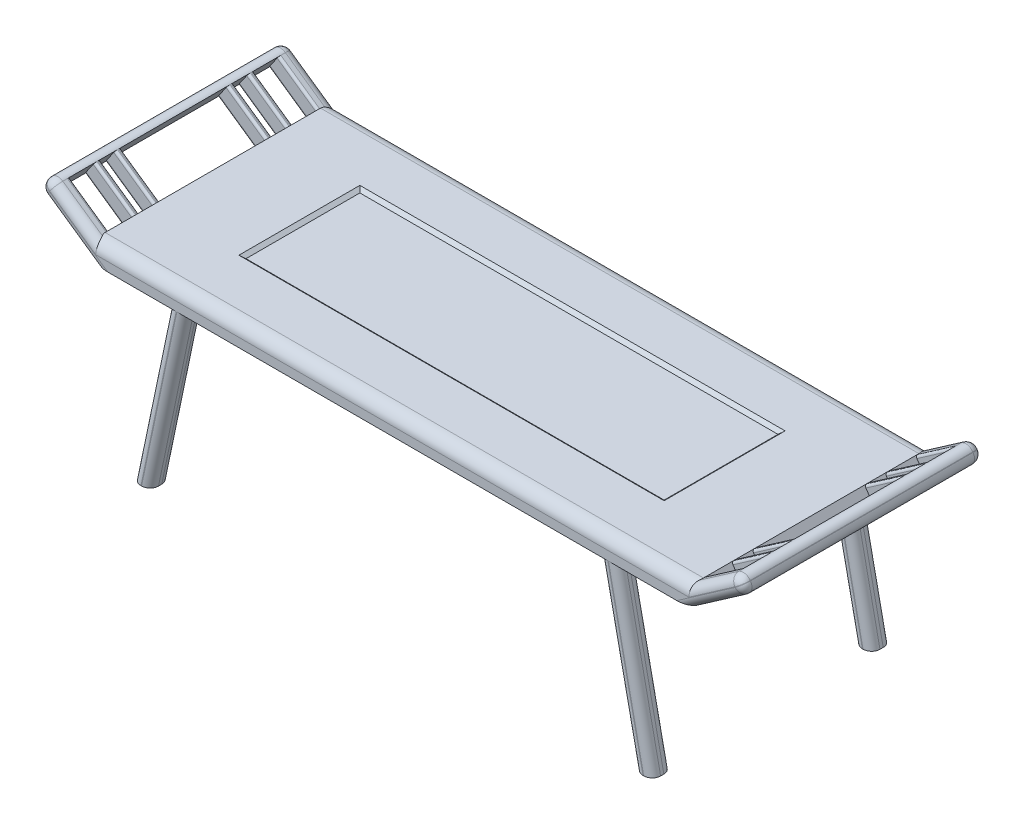
SolidWorks part; units mm, degrees
ref_plane "前视基准面" through (0, 0, 0) normal (0, 0, 1) x (1, 0, 0)
ref_plane "上视基准面" through (0, 0, 0) normal (0, 1, 0) x (1, 0, 0)
ref_plane "右视基准面" through (0, 0, 0) normal (1, 0, 0) x (0, 0, -1)
sketch "草图1" plane through (0, 0, 0) normal (0, 0, 1) x (1, 0, 0)
  line L0 (-576.1113, 70.4336) -> (-500, 17.5)
  line L1 (-500, 17.5) -> (500, 17.5)
  line L3 (-500, -17.5) -> (-375.437, -17.5)
  line L5 (576.1113, 70.4336) -> (500, 17.5)
  line L6 (576.1113, 70.4336) -> (592.5175, 46.8437)
  line L7 (500, 17.5) -> (576.1113, 70.4336)
  line L8 (-434.3541, -298.9117) -> (-404.7254, -298.9117) construction
  line L9 (-576.1113, 70.4336) -> (-500, 17.5)
  line L10 (-500, -17.5) -> (-592.5175, 46.8437)
  line L11 (-576.1113, 70.4336) -> (-592.5175, 46.8437)
  line L12 (-375.437, -17.5) -> (-434.3541, -298.9117)
  line L13 (-345.8082, -17.5) -> (345.8082, -17.5)
  line L16 (-434.3541, -298.9117) -> (-404.7254, -298.9117)
  line L17 (-345.8082, -17.5) -> (-404.7254, -298.9117)
  line L18 (500, -17.5) -> (592.5175, 46.8437)
  line L19 (500, -17.5) -> (375.437, -17.5)
  line L20 (434.3541, -298.9117) -> (404.7254, -298.9117)
  line L21 (375.437, -17.5) -> (434.3541, -298.9117)
  line L22 (345.8082, -17.5) -> (404.7254, -298.9117)
  line L23 (375.437, -17.5) -> (500, -17.5)
  line L24 (404.7254, -298.9117) -> (434.3541, -298.9117) construction
  line L25 (592.5175, 46.8437) -> (500, -17.5)
  line L26 (375.437, -17.5) -> (434.3541, -298.9117)
  line L27 (404.7254, -298.9117) -> (345.8082, -17.5)
  line L28 (-345.8082, -17.5) -> (-404.7254, -298.9117)
  line L29 (-434.3541, -298.9117) -> (-375.437, -17.5)
  line L30 (-500, -17.5) -> (-592.5175, 46.8437)
  line L31 (0, 312.9523) -> (0, -241.4471) construction
  point P0 (0, 0)
ref_plane "基准面1" through (0, 0, 0) normal (0, 0, 1) x (1, 0, 0)
sketch "草图2" plane through (0, 0, 0) normal (0, 0, 1) x (1, 0, 0)
  line L0 (-576.1113, 70.4336) -> (-500, 17.5)
  line L1 (-500, 17.5) -> (500, 17.5)
  line L2 (500, 17.5) -> (576.1113, 70.4336)
  line L3 (576.1113, 70.4336) -> (592.5175, 46.8437)
  line L4 (592.5175, 46.8437) -> (500, -17.5)
  line L5 (500, -17.5) -> (375.437, -17.5)
  line L6 (375.437, -17.5) -> (434.3541, -298.9117)
  line L7 (434.3541, -298.9117) -> (404.7254, -298.9117)
  line L8 (404.7254, -298.9117) -> (345.8082, -17.5)
  line L9 (345.8082, -17.5) -> (-345.8082, -17.5)
  line L10 (-345.8082, -17.5) -> (-404.7254, -298.9117)
  line L11 (-404.7254, -298.9117) -> (-434.3541, -298.9117)
  line L12 (-434.3541, -298.9117) -> (-375.437, -17.5)
  line L13 (-375.437, -17.5) -> (-500, -17.5)
  line L14 (-500, -17.5) -> (-592.5175, 46.8437)
  line L15 (-592.5175, 46.8437) -> (-576.1113, 70.4336)
extrude "凸台-拉伸1" add sketch "草图2" along normal blind 400
sketch "草图5" plane through (356.1615, 74.567, 0) normal (0.9788, 0.2049, 0) x (0, 0, -1)
  line L0 (-33.4207, -381.5762) -> (-33.4207, -94.0632)
  line L1 (-400, -381.5762) -> (0, -381.5762) construction
  line L2 (-400, -94.0632) -> (0, -94.0632) construction
  line L3 (-200, -381.5762) -> (-200, -200.9257) construction
  line L4 (-366.5793, -381.5762) -> (-366.5793, -94.0632)
  line L5 (-366.5793, -94.0632) -> (-33.4207, -94.0632)
  line L6 (-366.5793, -381.5762) -> (-33.4207, -381.5762)
extrude "切除-拉伸1" cut sketch "草图5" against normal blind 400
ref_plane "基准面3" through (0, 0, 0) normal (-1, 0, 0) x (0, 1, 0)
mirror "镜向1" about plane through (0, 0, 0) normal (-1, 0, 0) of "切除-拉伸1"
fillet "圆角1" radius 20 1 edges at (0, 17.5, 400)
fillet "圆角2" radius 20 1 edges at (0, 17.5, 0)
fillet "圆角3" radius 14 4 edges at (576.1113, 70.4336, 200) (592.5175, 46.8437, 200) (-592.5175, 46.8437, 200) (-576.1113, 70.4336, 200)
fillet "圆角4" radius 14 20 edges at (575.0861, 64.7259, 0) (584.3144, 58.6386, 0) (586.8098, 47.8688, 0) (-586.8098, 47.8688, 0) (-584.3144, 58.6386, 0) (-575.0861, 64.7259, 0) (586.8098, 47.8688, 400) (584.3144, 58.6386, 400) (575.0861, 64.7259, 400) (-586.8098, 47.8688, 400) (-584.3144, 58.6386, 400) (-575.0861, 64.7259, 400) (517.9302, 29.97, 0) (540.5119, 10.6751, 0) (-540.5119, 10.6751, 0) (-517.9302, 29.97, 0) (540.5119, 10.6751, 400) (517.9302, 29.97, 400) (-540.5119, 10.6751, 400) (-517.9302, 29.97, 400)
fillet "圆角5" radius 14 4 edges at (-404.8955, -158.2058, 366.5793) (-375.8889, -161.1772, 366.5793) (-375.2668, -158.2058, 400) (-404.8955, -158.2058, 400)
fillet "圆角6" radius 14 4 edges at (-375.8889, -161.1772, 33.4207) (-404.8955, -158.2058, 33.4207) (-375.2668, -158.2058, 0) (-404.8955, -158.2058, 0)
fillet "圆角7" radius 14 4 edges at (375.8889, -161.1772, 366.5793) (375.2668, -158.2058, 400) (404.8955, -158.2058, 400) (404.8955, -158.2058, 366.5793)
fillet "圆角8" radius 14 4 edges at (375.8889, -161.1772, 33.4207) (375.2668, -158.2058, 0) (404.8955, -158.2058, 33.4207) (404.8955, -158.2058, 0)
ref_plane "基准面4" through (154.7986, -222.5793, 0) normal (-0.571, 0.821, 0) x (0.821, 0.571, 0)
sketch "草图6" plane through (154.7986, -222.5793, 0) normal (-0.571, 0.821, 0) x (0.821, 0.571, 0)
  line L0 (420.4784, -66.9756) -> (499.187, -66.9756)
  line L1 (420.4784, -380) -> (420.4784, -20) construction
  line L2 (499.187, -386) -> (499.187, -14) construction
  line L3 (420.4784, -76.5219) -> (499.187, -76.5219)
  line L4 (420.4784, -101.3421) -> (499.187, -101.3421)
  line L5 (420.4784, -110.8883) -> (499.187, -110.8883)
  line L6 (420.4784, -25.6086) -> (499.187, -25.6086)
  line L7 (420.4784, -200) -> (499.187, -200) construction
  line L8 (420.4784, -374.3914) -> (499.187, -374.3914)
  line L9 (420.4784, -333.0244) -> (499.187, -333.0244)
  line L10 (420.4784, -323.4781) -> (499.187, -323.4781)
  line L11 (420.4784, -298.6579) -> (499.187, -298.6579)
  line L12 (420.4784, -289.1117) -> (499.187, -289.1117)
  line L13 (420.4784, -25.6086) -> (420.4784, -66.9756)
  line L14 (499.187, -25.6086) -> (499.187, -66.9756)
  line L15 (420.4784, -76.5219) -> (420.4784, -101.3421)
  line L16 (499.187, -76.5219) -> (499.187, -101.3421)
  line L17 (420.4784, -110.8883) -> (420.4784, -289.1117)
  line L18 (499.187, -110.8883) -> (499.187, -289.1117)
  line L19 (420.4784, -298.6579) -> (420.4784, -323.4781)
  line L20 (499.187, -298.6579) -> (499.187, -323.4781)
  line L21 (420.4784, -333.0244) -> (420.4784, -374.3914)
  line L22 (499.187, -333.0244) -> (499.187, -374.3914)
extrude "切除-拉伸2" cut sketch "草图6" against normal blind 400
mirror "镜向3" about plane through (0, 0, 0) normal (-1, 0, 0) of "切除-拉伸2"
fillet "圆角9" radius 4 20 edges at (548.715, 16.3801, 25.6086) (548.715, 16.3801, 66.9756) (548.715, 16.3801, 76.5219) (548.715, 16.3801, 101.3421) (548.715, 16.3801, 110.8883) (548.715, 16.3801, 289.1117) (548.715, 16.3801, 298.6579) (548.715, 16.3801, 323.4781) (548.715, 16.3801, 333.0244) (548.715, 16.3801, 374.3914) (532.3088, 39.97, 25.6086) (532.3088, 39.97, 374.3914) (532.3088, 39.97, 66.9756) (532.3088, 39.97, 76.5219) (532.3088, 39.97, 101.3421) (532.3088, 39.97, 110.8883) (532.3088, 39.97, 289.1117) (532.3088, 39.97, 298.6579) (532.3088, 39.97, 323.4781) (532.3088, 39.97, 333.0244)
fillet "圆角10" radius 4 15 edges at (-548.715, 16.3801, 25.6086) (-532.3088, 39.97, 374.3914) (-548.715, 16.3801, 374.3914) (-532.3088, 39.97, 25.6086) (-548.715, 16.3801, 101.3421) (-548.715, 16.3801, 66.9756) (-532.3088, 39.97, 66.9756) (-532.3088, 39.97, 76.5219) (-532.3088, 39.97, 101.3421) (-532.3088, 39.97, 110.8883) (-548.715, 16.3801, 289.1117) (-532.3088, 39.97, 289.1117) (-532.3088, 39.97, 298.6579) (-532.3088, 39.97, 323.4781) (-532.3088, 39.97, 333.0244)
fillet "圆角11" radius 4 3 edges at (-548.715, 16.3801, 333.0244) (-548.715, 16.3801, 323.4781) (-548.715, 16.3801, 298.6579)
fillet "圆角12" radius 4 2 edges at (-548.715, 16.3801, 76.5219) (-548.715, 16.3801, 110.8883)
sketch "草图7" plane through (0, 17.5, 0) normal (0, 1, 0) x (1, 0, 0)
  line L0 (0, -20) -> (0, -380) construction
  line L1 (500, -20) -> (-500, -20) construction
  line L2 (-500, -380) -> (500, -380) construction
  line L4 (-355.3306, -98.9254) -> (355.3306, -98.9254)
  line L5 (-355.3306, -98.9254) -> (-355.3306, -301.0746)
  line L6 (-355.3306, -301.0746) -> (355.3306, -301.0746)
  line L7 (355.3306, -98.9254) -> (355.3306, -301.0746)
  line L8 (-355.3306, -98.9254) -> (355.3306, -301.0746) construction
  line L9 (-355.3306, -301.0746) -> (355.3306, -98.9254) construction
  point P6 (0, -200)
extrude "切除-拉伸3" cut sketch "草图7" against normal blind 5 draft 50
sketch "草图9" plane through (0, -17.5, 0) normal (0, -1, 0) x (1, 0, 0)
  line L0 (0, 400) -> (0, 0) construction
  line L1 (-360.1117, 400) -> (360.1117, 400) construction
  circle A0 centre (0, 200) radius 59.825
extrude "切除-拉伸4" cut sketch "草图9" against normal blind 1
